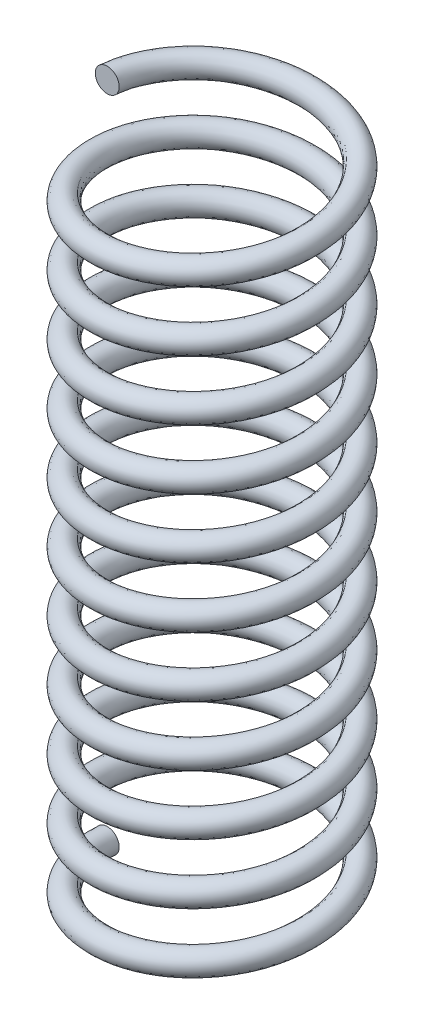
SolidWorks part; units mm, degrees
note: '?' marks a value the reader was unsure of.
ref_plane "Front Plane" through (0, 0, 0) normal (0, 0, 1) x (1, 0, 0)
ref_plane "Top Plane" through (0, 0, 0) normal (0, 1, 0) x (1, 0, 0)
ref_plane "Right Plane" through (0, 0, 0) normal (1, 0, 0) x (0, 0, -1)
sketch "Sketch1" plane through (0, 0, 0) normal (0, 1, 0) x (1, 0, 0)
  circle A0 centre (0, 0) radius 3.5
  dimension "D1" = 7
curve "Helix/Spiral1" pitch 2 height 22 turns 11
sketch "Sketch2" plane through (0, 0, 0) normal (0, 0, 1) x (1, 0, 0)
  line L0 (55, 0) -> (-55, 0) construction
  circle A0 centre (-3.5, 0) radius 0.4
  spline S0 degree 3 poles (-3.5, 0) (-3.5, 0.0414) (-3.3178, 0.1251) (-2.5393, 0.25) (-1.3743, 0.375) (0, 0.5) (1.3743, 0.625) (2.5393, 0.75) (3.3178, 0.875) (3.5911, 1) (3.3178, 1.125) (2.5393, 1.25) (1.3743, 1.375) (0, 1.5) (-1.3743, 1.625) (-2.5393, 1.75) (-3.3178, 1.875) (-3.5911, 2) (-3.3178, 2.125) (-2.5393, 2.25) (-1.3743, 2.375) (0, 2.5) (1.3743, 2.625) (2.5393, 2.75) (3.3178, 2.875) (3.5911, 3) (3.3178, 3.125) (2.5393, 3.25) (1.3743, 3.375) (0, 3.5) (-1.3743, 3.625) (-2.5393, 3.75) (-3.3178, 3.875) (-3.5911, 4) (-3.3178, 4.125) (-2.5393, 4.25) (-1.3743, 4.375) (0, 4.5) (1.3743, 4.625) (2.5393, 4.75) (3.3178, 4.875) (3.5911, 5) (3.3178, 5.125) (2.5393, 5.25) (1.3743, 5.375) (0, 5.5) (-1.3743, 5.625) (-2.5393, 5.75) (-3.3178, 5.875) (-3.5911, 6) (-3.3178, 6.125) (-2.5393, 6.25) (-1.3743, 6.375) (0, 6.5) (1.3743, 6.625) (2.5393, 6.75) (3.3178, 6.875) (3.5911, 7) (3.3178, 7.125) (2.5393, 7.25) (1.3743, 7.375) (0, 7.5) (-1.3743, 7.625) (-2.5393, 7.75) (-3.3178, 7.875) (-3.5911, 8) (-3.3178, 8.125) (-2.5393, 8.25) (-1.3743, 8.375) (0, 8.5) (1.3743, 8.625) (2.5393, 8.75) (3.3178, 8.875) (3.5911, 9) (3.3178, 9.125) (2.5393, 9.25) (1.3743, 9.375) (0, 9.5) (-1.3743, 9.625) (-2.5393, 9.75) (-3.3178, 9.875) (-3.5911, 10) (-3.3178, 10.125) (-2.5393, 10.25) (-1.3743, 10.375) (0, 10.5) (1.3743, 10.625) (2.5393, 10.75) (3.3178, 10.875) (3.5911, 11) (3.3178, 11.125) (2.5393, 11.25) (1.3743, 11.375) (0, 11.5) (-1.3743, 11.625) (-2.5393, 11.75) (-3.3178, 11.875) (-3.5911, 12) (-3.3178, 12.125) (-2.5393, 12.25) (-1.3743, 12.375) (0, 12.5) (1.3743, 12.625) (2.5393, 12.75) (3.3178, 12.875) (3.5911, 13) (3.3178, 13.125) (2.5393, 13.25) (1.3743, 13.375) (0, 13.5) (-1.3743, 13.625) (-2.5393, 13.75) (-3.3178, 13.875) (-3.5911, 14) (-3.3178, 14.125) (-2.5393, 14.25) (-1.3743, 14.375) (0, 14.5) (1.3743, 14.625) (2.5393, 14.75) (3.3178, 14.875) (3.5911, 15) (3.3178, 15.125) (2.5393, 15.25) (1.3743, 15.375) (0, 15.5) (-1.3743, 15.625) (-2.5393, 15.75) (-3.3178, 15.875) (-3.5911, 16) (-3.3178, 16.125) (-2.5393, 16.25) (-1.3743, 16.375) (0, 16.5) (1.3743, 16.625) (2.5393, 16.75) (3.3178, 16.875) (3.5911, 17) (3.3178, 17.125) (2.5393, 17.25) (1.3743, 17.375) (0, 17.5) (-1.3743, 17.625) (-2.5393, 17.75) (-3.3178, 17.875) (-3.5911, 18) (-3.3178, 18.125) (-2.5393, 18.25) (-1.3743, 18.375) (0, 18.5) (1.3743, 18.625) (2.5393, 18.75) (3.3178, 18.875) (3.5911, 19) (3.3178, 19.125) (2.5393, 19.25) (1.3743, 19.375) (0, 19.5) (-1.3743, 19.625) (-2.5393, 19.75) (-3.3178, 19.875) (-3.5911, 20) (-3.3178, 20.125) (-2.5393, 20.25) (-1.3743, 20.375) (0, 20.5) (1.3743, 20.625) (2.5393, 20.75) (3.3178, 20.875) (3.5911, 21) (3.3178, 21.125) (2.5393, 21.25) (1.3743, 21.375) (0, 21.5) (-1.3743, 21.625) (-2.5393, 21.75) (-3.3178, 21.8749) (-3.5, 21.9586) (-3.5, 22) knots 0 0 0 0 0.005682 0.011364 0.017045 0.022727 0.028409 0.034091 0.039773 0.045455 0.051136 0.056818 0.0625 0.068182 0.073864 0.079545 0.085227 0.090909 0.096591 0.102273 0.107955 0.113636 0.119318 0.125 0.130682 0.136364 0.142045 0.147727 0.153409 0.159091 0.164773 0.170455 0.176136 0.181818 0.1875 0.193182 0.198864 0.204545 0.210227 0.215909 0.221591 0.227273 0.232955 0.238636 0.244318 0.25 0.255682 0.261364 0.267045 0.272727 0.278409 0.284091 0.289773 0.295455 0.301136 0.306818 0.3125 0.318182 0.323864 0.329545 0.335227 0.340909 0.346591 0.352273 0.357955 0.363636 0.369318 0.375 0.380682 0.386364 0.392045 0.397727 0.403409 0.409091 0.414773 0.420455 0.426136 0.431818 0.4375 0.443182 0.448864 0.454545 0.460227 0.465909 0.471591 0.477273 0.482955 0.488636 0.494318 0.5 0.505682 0.511364 0.517045 0.522727 0.528409 0.534091 0.539773 0.545455 0.551136 0.556818 0.5625 0.568182 0.573864 0.579545 0.585227 0.590909 0.596591 0.602273 0.607955 0.613636 0.619318 0.625 0.630682 0.636364 0.642045 0.647727 0.653409 0.659091 0.664773 0.670455 0.676136 0.681818 0.6875 0.693182 0.698864 0.704545 0.710227 0.715909 0.721591 0.727273 0.732955 0.738636 0.744318 0.75 0.755682 0.761364 0.767045 0.772727 0.778409 0.784091 0.789773 0.795455 0.801136 0.806818 0.8125 0.818182 0.823864 0.829545 0.835227 0.840909 0.846591 0.852273 0.857955 0.863636 0.869318 0.875 0.880682 0.886364 0.892045 0.897727 0.903409 0.909091 0.914773 0.920455 0.926136 0.931818 0.9375 0.943182 0.948864 0.954545 0.960227 0.965909 0.971591 0.977273 0.982955 0.988636 0.994318 1 1 1 1 construction
  dimension "D1" = 0.8
sweep "Sweep1" add profiles "Sketch2" path "Helix/Spiral1"
ref_axis "Axis1" through (0, -1.0525, 0) along (0, 1, 0)?
ref_plane "Plane1" through (0, 22, 0) normal (0, 1, 0) x (1, 0, 0)
